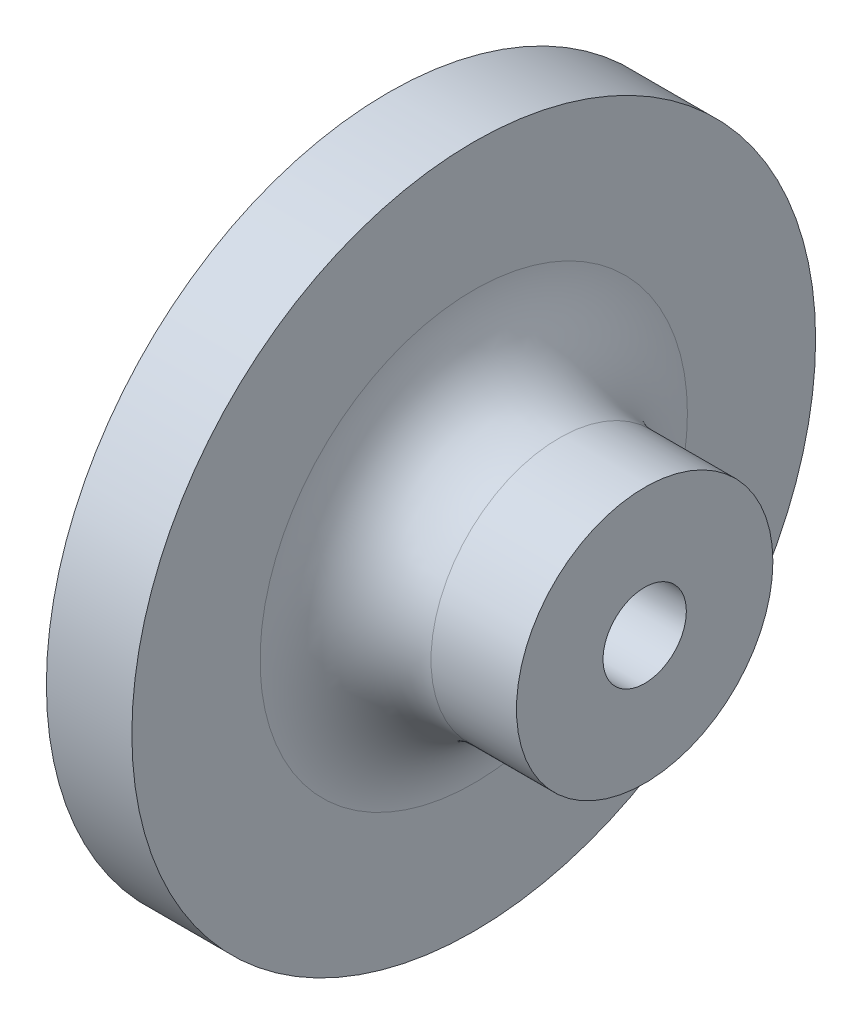
SolidWorks part; units mm, degrees
ref_plane "Plan de face" through (0, 0, 0) normal (1, 0, 0) x (0, 1, 0)
ref_plane "Plan de dessus" through (0, 0, 0) normal (0, 0, 1) x (0, 1, 0)
ref_plane "Plan de droite" through (0, 0, 0) normal (0, 1, 0) x (-1, 0, 0)
sketch "Esquisse1" plane through (0, 0, 0) normal (1, 0, 0) x (0, 1, 0)
  circle A0 centre (0, 0) radius 40
  circle A1 centre (0, 32) radius 5.5
  circle A2 centre (12.2459, 29.5641) radius 5.5
  circle A3 centre (22.6274, 22.6274) radius 5.5
  circle A4 centre (29.5641, 12.2459) radius 5.5
  circle A5 centre (32, 0) radius 5.5
  circle A6 centre (29.5641, -12.2459) radius 5.5
  circle A7 centre (22.6274, -22.6274) radius 5.5
  circle A8 centre (12.2459, -29.5641) radius 5.5
  circle A9 centre (0, -32) radius 5.5
  circle A10 centre (-12.2459, -29.5641) radius 5.5
  circle A11 centre (-22.6274, -22.6274) radius 5.5
  circle A12 centre (-29.5641, -12.2459) radius 5.5
  circle A13 centre (-32, 0) radius 5.5
  circle A14 centre (-29.5641, 12.2459) radius 5.5
  circle A15 centre (-22.6274, 22.6274) radius 5.5
  circle A16 centre (-12.2459, 29.5641) radius 5.5
  circle A17 centre (-11.4293, 17.1051) radius 5.5
  circle A18 centre (4.0134, 20.1768) radius 5.5
  circle A19 centre (17.1051, 11.4293) radius 5.5
  circle A20 centre (20.1768, -4.0134) radius 5.5
  circle A21 centre (11.4293, -17.1051) radius 5.5
  circle A22 centre (-4.0134, -20.1768) radius 5.5
  circle A23 centre (-17.1051, -11.4293) radius 5.5
  circle A24 centre (-20.1768, 4.0134) radius 5.5
  circle A25 centre (5.5277, 8.2728) radius 5.5
  circle A26 centre (8.2728, -5.5277) radius 5.5
  circle A27 centre (-5.5277, -8.2728) radius 5.5
  circle A28 centre (-8.2728, 5.5277) radius 5.5
  point P37 (0, 0)
  point P54 (0, 0)
  point P64 (0, 0)
  dimension "D1" = 80
  dimension "D2" = 11
  dimension "D5" = 11
  dimension "D9" = 11
  dimension "D3" = 32
  dimension "D6" = 12.4858
  dimension "D7" = 12.4858
  dimension "D10" = 12
  dimension "D11" = 12
  dimension "D4" = 16
  dimension "D8" = 8
  dimension "D12" = 4
extrude "Boss.-Extru.1" add sketch "Esquisse1" along normal blind 10
sketch "Esquisse2" plane through (10, 0, 0) normal (1, 0, 0) x (0, 1, 0)
  circle A0 centre (0, 0) radius 40
extrude "Boss.-Extru.2" add sketch "Esquisse2" against normal blind 7
sketch "Esquisse3" plane through (10, 0, 0) normal (1, 0, 0) x (0, 1, 0)
  circle A0 centre (0, 0) radius 15
  dimension "D1" = 30
extrude "Boss.-Extru.3" add sketch "Esquisse3" along normal blind 20
fillet "Congé1" radius 10 1 edges at (10, 0, -15)
sketch "Esquisse4" plane through (30, 0, 0) normal (1, 0, 0) x (0, 1, 0)
  circle A0 centre (0, 0) radius 4.875
  dimension "D1" = 9.75
extrude "Enlèv. mat.-Extru.1" cut sketch "Esquisse4" against normal blind 16
sketch "Esquisse5" plane through (0, 0, 0) normal (-1, 0, 0) x (0, -1, 0)
  line L0 (8.0378, 39.1841) -> (-8.0378, -39.1841) construction
  circle A0 centre (0, 0) radius 40 construction
  point P4 (0, 0)
